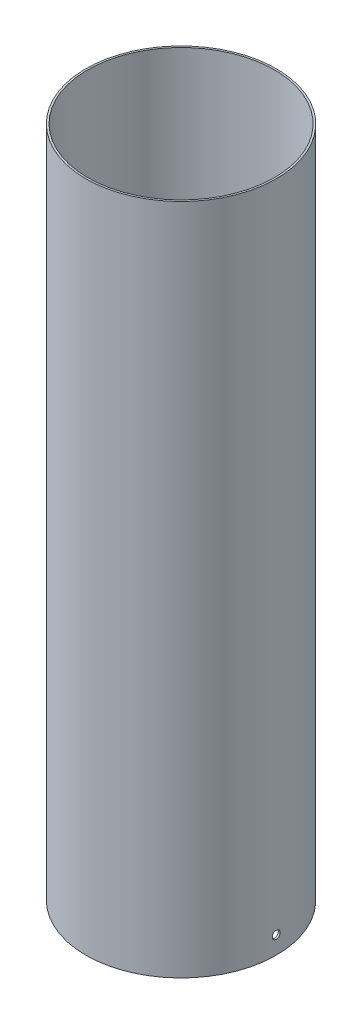
SolidWorks part; units mm, degrees
material "PBT Общее назначение"
ref_plane "Спереди" through (0, 0, 0) normal (0, 0, 1) x (1, 0, 0)
ref_plane "Сверху" through (0, 0, 0) normal (0, 1, 0) x (1, 0, 0)
ref_plane "Справа" through (0, 0, 0) normal (1, 0, 0) x (0, 0, -1)
sketch "Эскиз1" plane through (0, 0, 0) normal (0, 1, 0) x (1, 0, 0)
  circle A0 centre (0, 0) radius 51
  circle A1 centre (0, 0) radius 50
  dimension "D1" = 100
  dimension "D2" = 102
extrude "Бобышка-Вытянуть1" add sketch "Эскиз1" along normal blind 360
sketch "Эскиз2" plane through (0, 0, 0) normal (1, 0, 0) x (0, 0, -1)
  line L0 (0, 0) -> (0, 360) construction
  line L1 (50, 360) -> (-50, 360) construction
  circle A0 centre (0, 9.5) radius 2.1
  dimension "D1" = 4.2
  dimension "D2" = 9.5
extrude "Вырез-Вытянуть1" cut sketch "Эскиз2" against normal blind 129 and the other way blind 116
